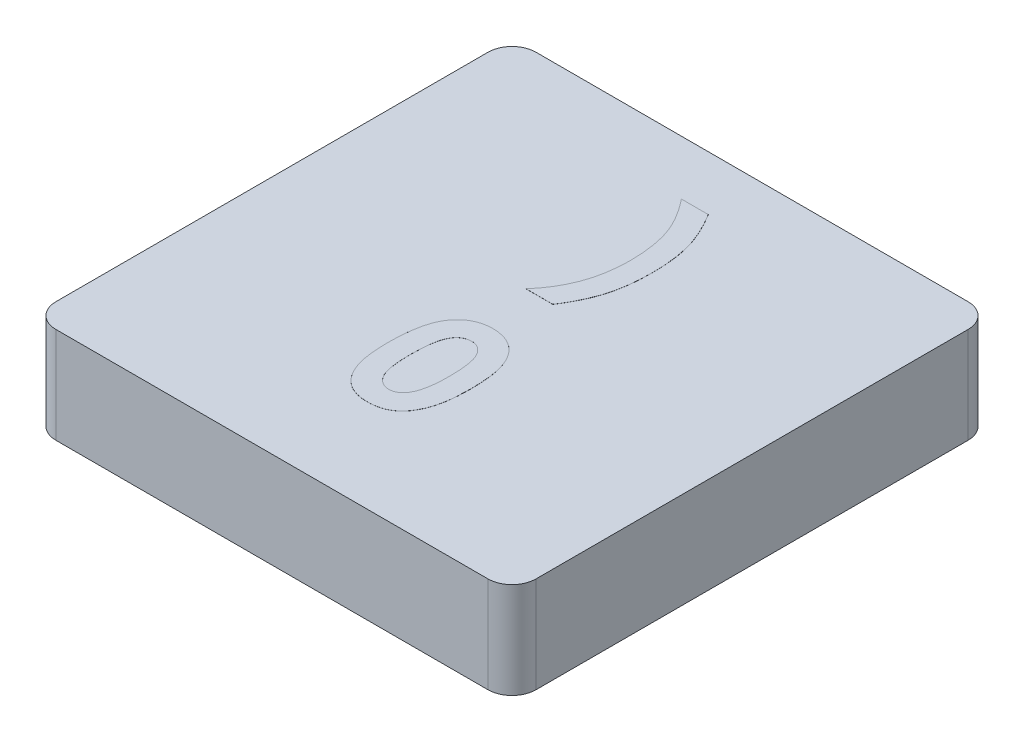
SolidWorks part; units mm, degrees
ref_plane "Front Plane" through (0, 0, 0) normal (0, 0, 1) x (1, 0, 0)
ref_plane "Top Plane" through (0, 0, 0) normal (0, 1, 0) x (1, 0, 0)
ref_plane "Right Plane" through (0, 0, 0) normal (1, 0, 0) x (0, 0, -1)
sketch "Sketch1" plane through (0, 0, 0) normal (0, 1, 0) x (1, 0, 0)
  line L0 (0, 0) -> (12.7, 0)
  line L1 (12.7, 0) -> (12.7, 12.7)
  line L2 (12.7, 12.7) -> (0, 12.7)
  line L3 (0, 12.7) -> (0, 0)
  dimension "D1" = 12.7
  dimension "D2" = 12.7
extrude "Boss-Extrude1" add sketch "Sketch1" along normal blind 2.54
fillet "Fillet1" radius 0.635 4 edges at (0, 1.27, -12.7) (12.7, 1.27, -12.7) (12.7, 1.27, 0) (0, 1.27, 0)
shell "Shell1" thickness 0.635 removed face at (6.35, 0, -6.35)
sketch "Sketch2" plane through (0, 1.905, 0) normal (0, -1, 0) x (-1, 0, 0)
  line L0 (-0.635, 6.35) -> (-12.065, 6.35) construction
  line L1 (-0.635, 12.065) -> (-0.635, 0.635) construction
  line L2 (-12.065, 0.635) -> (-12.065, 12.065) construction
  line L3 (-6.35, 0.635) -> (-6.35, 12.065) construction
  line L4 (-0.635, 0.635) -> (-12.065, 0.635) construction
  line L5 (-12.065, 12.065) -> (-0.635, 12.065) construction
  circle A0 centre (-6.35, 6.35) radius 2.54
  dimension "D1" = 5.08
extrude "Boss-Extrude2" add sketch "Sketch2" along normal up to surface (1.905 mm away) up to face at (6.35, 0, -6.35)
sketch "Sketch4" plane through (0, 2.54, 0) normal (0, 1, 0) x (1, 0, 0)
  line L0 (0, 12.065) -> (0, 0.635) construction
  line L1 (12.065, 12.7) -> (0.635, 12.7) construction
  line L2 (0.635, 0) -> (12.065, 0) construction
  text T0 "<b>0</b>"
  text T1 "<b>)</b>"
  dimension "D1" = 5.842
  dimension "D2" = 5.207
  dimension "D3" = 4.699
  dimension "D4" = 2.54
extrude "Boss-Extrude4" add sketch "Sketch4" along normal blind 0.0025
